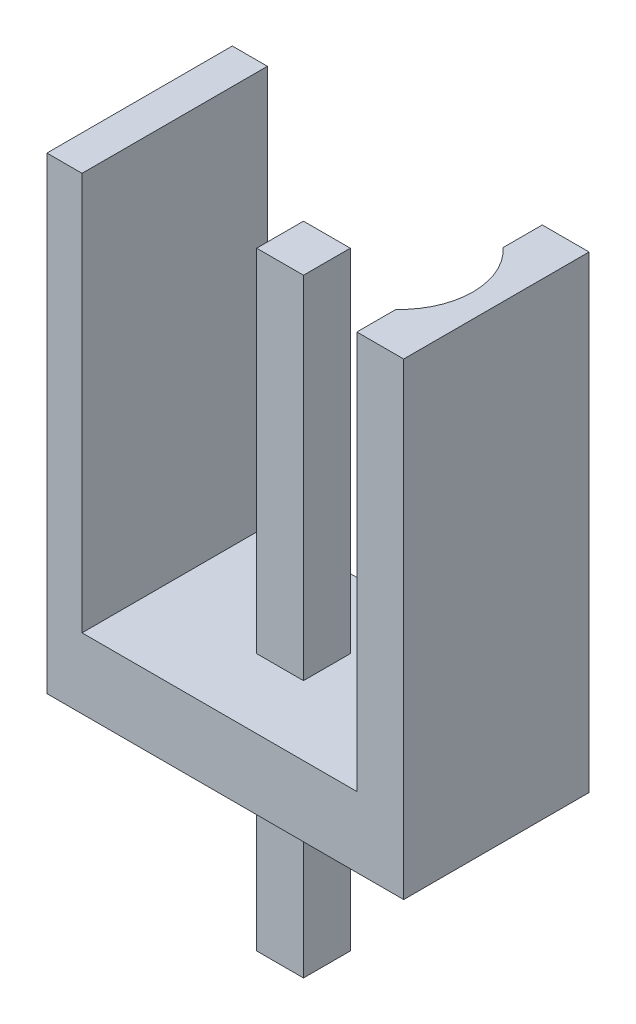
SolidWorks part; units mm, degrees
ref_plane "前视基准面" through (0, 0, 0) normal (0, 0, 1) x (1, 0, 0)
ref_plane "上视基准面" through (0, 0, 0) normal (0, 1, 0) x (1, 0, 0)
ref_plane "右视基准面" through (0, 0, 0) normal (1, 0, 0) x (0, 0, -1)
sketch "草图1" plane through (0, 0, 0) normal (0, 1, 0) x (1, 0, 0)
  line L0 (0, 11.3571) -> (0, -8.6742) construction
  line L1 (-3.81, 1.98) -> (3.81, 1.98)
  line L2 (-3.81, 1.98) -> (-3.81, -1.98)
  line L3 (-3.81, -1.98) -> (3.81, -1.98)
  line L4 (3.81, 1.98) -> (3.81, -1.98)
  line L5 (-11.8577, 0) -> (16.1453, 0) construction
  dimension "D1" = 7.62
  dimension "D2" = 3.96
extrude "拉伸1" add sketch "草图1" along normal blind 10
sketch "草图2" plane through (0, 10, 0) normal (0, 1, 0) x (-1, 0, 0)
  line L0 (-4.9146, 0) -> (4.5942, 0) construction
  line L1 (-1.7494, 0) -> (-4.2075, 0) construction
  line L2 (-2.81, 1.1448) -> (-2.81, 1.98)
  line L3 (-3.81, 1.98) -> (-3.81, -1.98) construction
  line L4 (-2.81, -1.1448) -> (-2.81, -1.98)
  line L5 (-3.31, 0) -> (-3.31, -3.9781) construction
  line L7 (3.06, -1.98) -> (3.06, 1.98)
  line L8 (-3.81, -1.98) -> (3.81, -1.98) construction
  line L9 (3.81, -1.98) -> (3.81, 1.98) construction
  line L10 (-2.81, 1.98) -> (3.06, 1.98)
  line L14 (-2.81, -1.98) -> (3.06, -1.98)
  arc A1 (-2.81, 1.1448) -> (-2.81, -1.1448) centre (-1.7494, 0) ccw
  point P16 (-2.81, 0)
  point P25 (3.06, 0)
  dimension "D1" = 1
  dimension "D2" = 1.5606
  dimension "D4" = 0.5
  dimension "D5" = 0.75
extrude "切除-拉伸1" cut sketch "草图2" against normal offset from surface (8.5 mm away) 1.5 up to face at (0, 0, 0)
sketch "草图3" plane through (0, 0, 0) normal (0, -1, 0) x (1, 0, 0)
  line L0 (4.5117, 0) -> (-4.6667, 0) construction
  line L1 (2.1187, 0) -> (-2.5308, 0) construction
  line L2 (0.19, 0.5) -> (-0.81, 0.5)
  line L3 (0.19, 0.5) -> (0.19, -0.5)
  line L4 (0.19, -0.5) -> (-0.81, -0.5)
  line L5 (-0.81, 0.5) -> (-0.81, -0.5)
  line L6 (-0.31, 3.5474) -> (-0.31, 0.8266) construction
  line L7 (-3.81, -1.98) -> (-3.81, 1.98) construction
  dimension "D1" = 1
  dimension "D2" = 1
  dimension "D4" = 3.5
extrude "拉伸2" add sketch "草图3" along normal blind 4 and the other way offset from surface 1 other way up to face at (-3.435, 10, 0)
